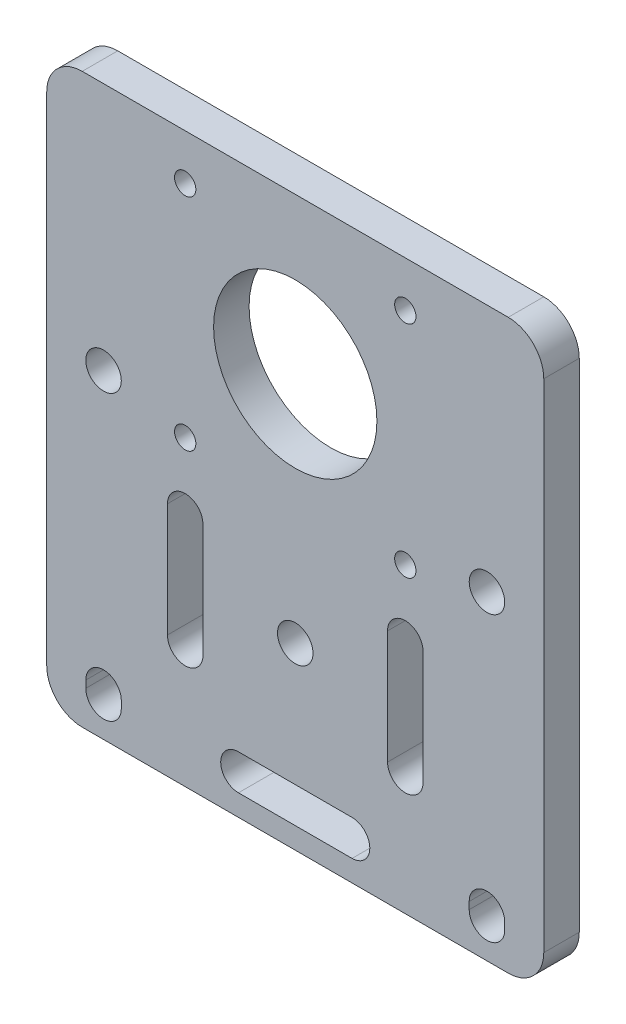
SolidWorks part; units mm, degrees
ref_plane "Front" through (0, 0, 0) normal (0, 0, 1) x (1, 0, 0)
ref_plane "Top" through (0, 0, 0) normal (0, 1, 0) x (1, 0, 0)
ref_plane "Right" through (0, 0, 0) normal (1, 0, 0) x (0, 0, -1)
sketch "Sketch4" plane through (0, 0, 0) normal (0, 0, 1) x (1, 0, 0)
  line L0 (-27, -34) -> (-27, -35) construction
  line L1 (-35, 40) -> (35, 40)
  line L2 (-35, 40) -> (-35, -40)
  line L3 (-35, -40) -> (35, -40)
  line L4 (35, 40) -> (35, -40)
  line L5 (-35, 40) -> (35, -40) construction
  line L6 (-35, -40) -> (35, 40) construction
  line L7 (-24.5, -34) -> (-24.5, -35)
  line L8 (-29.5, -34) -> (-29.5, -35)
  line L9 (0, -47.1607) -> (0, 39.6245) construction
  line L10 (27, -34) -> (27, -35) construction
  line L11 (24.5, -34) -> (24.5, -35)
  line L12 (29.5, -34) -> (29.5, -35)
  circle A0 centre (-27, 5) radius 2.5
  arc A1 (-24.5, -34) -> (-29.5, -34) centre (-27, -34) ccw
  arc A2 (-29.5, -35) -> (-24.5, -35) centre (-27, -35) ccw
  arc A3 (24.5, -34) -> (29.5, -34) centre (27, -34) cw
  arc A4 (29.5, -35) -> (24.5, -35) centre (27, -35) cw
  circle A5 centre (27, 5) radius 2.5
  point P0 (0, 0)
  point P10 (-27, -34.5)
  point P19 (27, -34.5)
  dimension "D3" = 27
  dimension "D6" = 2.5
  dimension "D1" = 70
  dimension "D2" = 80
  dimension "D4" = 39
  dimension "D5" = 1
  dimension "D7" = 5
extrude "Boss-Extrude2" add sketch "Sketch4" along normal blind 5
sketch "Sketch5" plane through (0, 0, 5) normal (0, 0, 1) x (1, 0, 0)
  line L0 (0, 46.583) -> (0, -17.262) construction
  line L1 (-44.8343, 18.0767) -> (52.8956, 18.0767) construction
  line L2 (-27, 5) -> (27, -34.5) construction
  line L3 (-27, -34.5) -> (27, 5) construction
  line L4 (-8, -34.5) -> (8, -34.5) construction
  line L5 (-8, -32) -> (8, -32)
  line L6 (-8, -37) -> (8, -37)
  line L7 (-15.5, -6.75) -> (-15.5, -22.75) construction
  line L8 (-13, -6.75) -> (-13, -22.75)
  line L9 (-18, -6.75) -> (-18, -22.75)
  line L10 (0, -5.3618) -> (0, -23.281) construction
  line L11 (15.5, -6.75) -> (15.5, -22.75) construction
  line L12 (13, -6.75) -> (13, -22.75)
  line L13 (18, -6.75) -> (18, -22.75)
  circle A0 centre (0, 18.0767) radius 11.5
  circle A1 centre (27, 5) radius 2.5 construction
  circle A2 centre (-15.5, 33.5767) radius 1.5
  circle A9 centre (15.5, 33.5767) radius 1.5
  circle A10 centre (15.5, 2.5767) radius 1.5
  circle A11 centre (-15.5, 2.5767) radius 1.5
  circle A12 centre (0, -14.75) radius 2.5
  arc A13 (-8, -32) -> (-8, -37) centre (-8, -34.5) ccw
  arc A14 (8, -37) -> (8, -32) centre (8, -34.5) ccw
  arc A15 (-13, -6.75) -> (-18, -6.75) centre (-15.5, -6.75) ccw
  arc A16 (-18, -22.75) -> (-13, -22.75) centre (-15.5, -22.75) ccw
  arc A17 (13, -6.75) -> (18, -6.75) centre (15.5, -6.75) cw
  arc A18 (18, -22.75) -> (13, -22.75) centre (15.5, -22.75) cw
  point P26 (0, -34.5)
  point P33 (-15.5, -14.75)
  point P42 (15.5, -14.75)
  point P47 (0, 0)
  point P48 (0, 0)
  dimension "D1" = 23
  dimension "D3" = 3
  dimension "D6" = 16
  dimension "D7" = 2.5
  dimension "D9" = 2.5
  dimension "D10" = 5
  dimension "D2" = 30
  dimension "D4" = 15.5
  dimension "D5" = 15.5
  dimension "D8" = 16
extrude "Cut-Extrude2" cut sketch "Sketch5" against normal through all
fillet "Fillet1" radius 5 4 edges at (-35, -40, 2.5) (35, -40, 2.5) (35, 40, 2.5) (-35, 40, 2.5)
